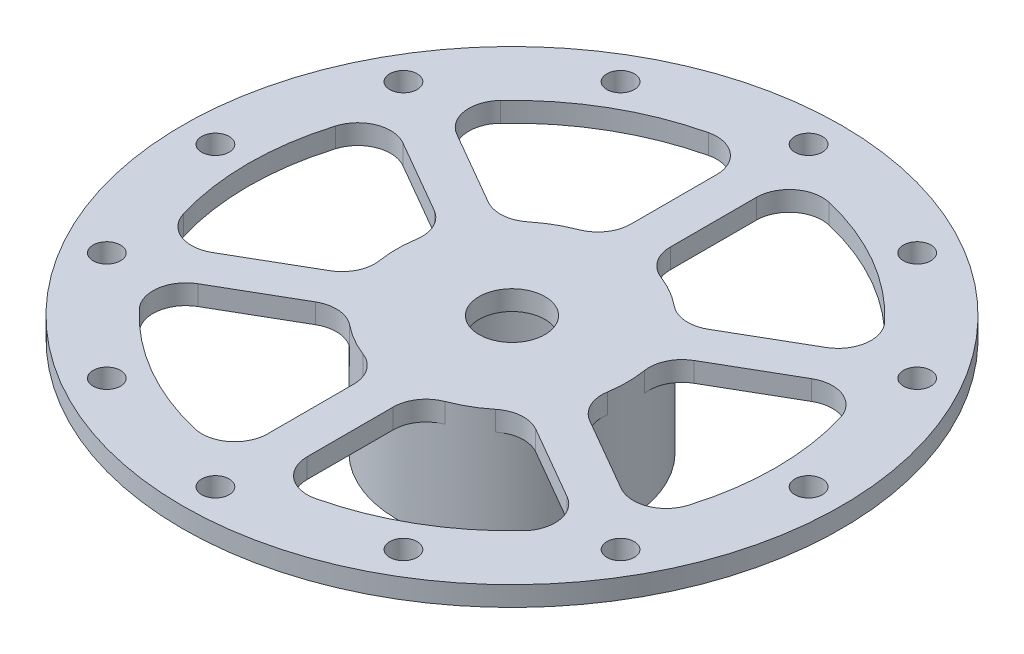
SolidWorks part; units mm, degrees
ref_plane "Front Plane" through (0, 0, 0) normal (0, 0, 1) x (1, 0, 0)
ref_plane "Top Plane" through (0, 0, 0) normal (0, 1, 0) x (1, 0, 0)
ref_plane "Right Plane" through (0, 0, 0) normal (1, 0, 0) x (0, 0, -1)
sketch "Sketch1" plane through (0, 0, 0) normal (0, 1, 0) x (1, 0, 0)
  line L0 (0, 62.3937) -> (0, -64.9792) construction
  line L1 (-3, 39.8873) -> (-3, 17.2409)
  line L2 (3, 39.8873) -> (3, 17.2409)
  line L3 (33.0435, 22.5417) -> (13.4311, 11.2185)
  line L4 (36.0435, 17.3456) -> (16.4311, 6.0224)
  line L5 (36.0435, -17.3456) -> (16.4311, -6.0224)
  line L6 (33.0435, -22.5417) -> (13.4311, -11.2185)
  line L7 (3, -39.8873) -> (3, -17.2409)
  line L8 (-3, -39.8873) -> (-3, -17.2409)
  line L9 (-33.0435, -22.5417) -> (-13.4311, -11.2185)
  line L10 (-36.0435, -17.3456) -> (-16.4311, -6.0224)
  line L11 (-36.0435, 17.3456) -> (-16.4311, 6.0224)
  line L12 (-33.0435, 22.5417) -> (-13.4311, 11.2185)
  circle A0 centre (0, 0) radius 50
  circle A1 centre (0, 0) radius 40
  circle A2 centre (0, 0) radius 14.5 construction
  circle A3 centre (0, 0) radius 5
  circle A4 centre (0, 0) radius 17.5
  circle A5 centre (0, 45) radius 2.0828
  circle A6 centre (22.5, 38.9711) radius 2.0828
  circle A7 centre (38.9711, 22.5) radius 2.0828
  circle A8 centre (45, 0) radius 2.0828
  circle A9 centre (38.9711, -22.5) radius 2.0828
  circle A10 centre (22.5, -38.9711) radius 2.0828
  circle A11 centre (0, -45) radius 2.0828
  circle A12 centre (-22.5, -38.9711) radius 2.0828
  circle A13 centre (-38.9711, -22.5) radius 2.0828
  circle A14 centre (-45, 0) radius 2.0828
  circle A15 centre (-38.9711, 22.5) radius 2.0828
  circle A16 centre (-22.5, 38.9711) radius 2.0828
  circle A17 centre (0, 0) radius 40
  circle A18 centre (0, 0) radius 40
  circle A19 centre (0, 0) radius 40
  circle A20 centre (0, 0) radius 40
  circle A21 centre (0, 0) radius 40
  point P35 (0, 0)
  point P65 (0, 0)
  dimension "D1" = 100
  dimension "D2" = 29
  dimension "D3" = 10
  dimension "D4" = 3
  dimension "D5" = 80
  dimension "D6" = 4.1656
  dimension "D7" = 45
  dimension "D9" = 3
  dimension "D10" = 3
  dimension "D8" = 12
  dimension "D11" = 6
extrude "Boss-Extrude1" add sketch "Sketch1" along normal blind 3 contours A0 A16 A15 A14 A13 A12 A11 A10 A9 A8 A7 A6 A5 A1 | A4 L10 A1 L9 | A4 L12 A1 L11 | A4 L2 A1 L1 | A4 L4 A1 L3 | A4 L6 A1 L5 | A4 L8 A1 L7 | A4 A3 region at (0, 0, -28.6881) region at (0, 0, -17.005) region at (-24.8446, 0, -14.344) region at (24.8446, 0, -14.344) region at (-24.8446, 0, 14.344) region at (24.8446, 0, 14.344) region at (0, 0, 28.6881) region at (-48.5858, 0, 0)
sketch "Sketch2" plane through (0, 0, 0) normal (0, -1, 0) x (1, 0, 0)
  circle A0 centre (0, 0) radius 17.5
  circle A1 centre (0, 0) radius 14.5
  dimension "D1" = 29
  dimension "D2" = 35
extrude "Boss-Extrude2" add sketch "Sketch2" along normal blind 15
fillet "Fillet1" radius 5 24 edges at (16.4311, 1.5, -6.0224) (36.0435, 1.5, -17.3456) (36.0435, 1.5, 17.3456) (16.4311, 1.5, 6.0224) (33.0435, 1.5, -22.5417) (13.4311, 1.5, -11.2185) (3, 1.5, -17.2409) (3, 1.5, -39.8873) (-3, 1.5, -39.8873) (-3, 1.5, -17.2409) (-13.4311, 1.5, -11.2185) (-33.0435, 1.5, -22.5417) (-36.0435, 1.5, -17.3456) (-16.4311, 1.5, -6.0224) (-16.4311, 1.5, 6.0224) (-36.0435, 1.5, 17.3456) (-3, 1.5, 39.8873) (-33.0435, 1.5, 22.5417) (-13.4311, 1.5, 11.2185) (-3, 1.5, 17.2409) (3, 1.5, 39.8873) (3, 1.5, 17.2409) (13.4311, 1.5, 11.2185) (33.0435, 1.5, 22.5417)
